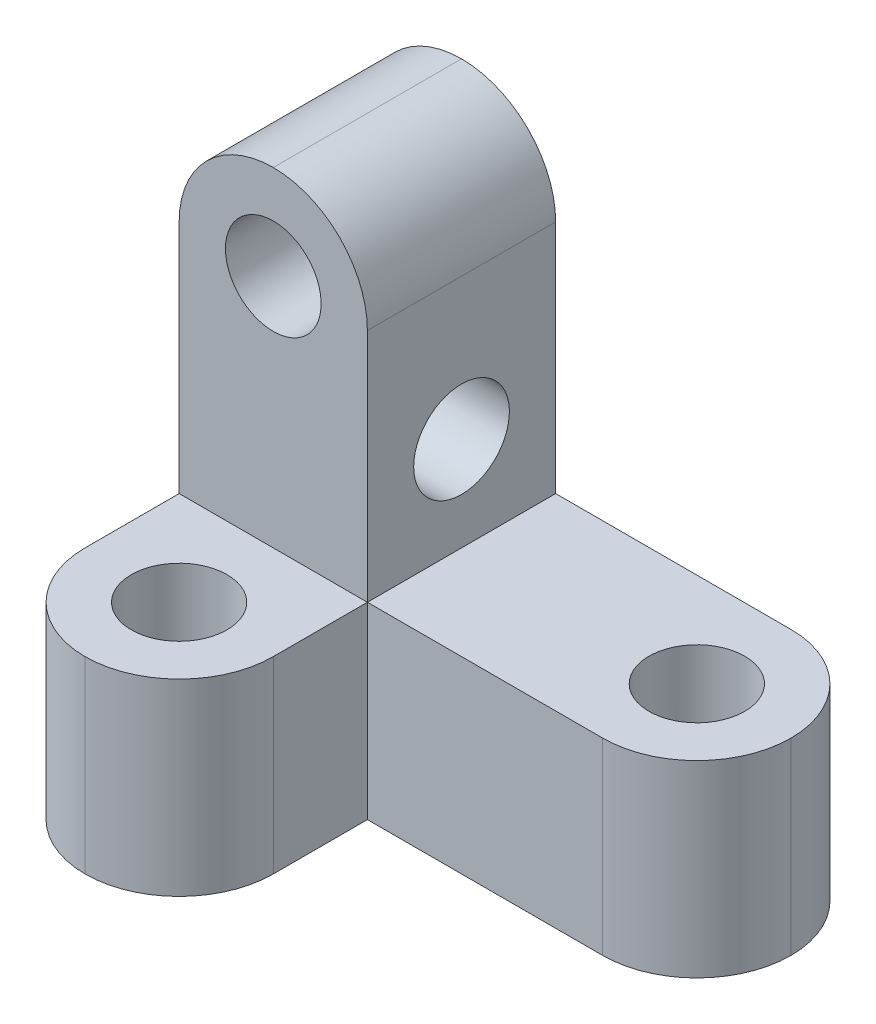
SolidWorks part; units mm, degrees
ref_plane "Front Plane" through (0, 0, 0) normal (0, 0, 1) x (1, 0, 0)
ref_plane "Top Plane" through (0, 0, 0) normal (0, 1, 0) x (1, 0, 0)
ref_plane "Right Plane" through (0, 0, 0) normal (1, 0, 0) x (0, 0, -1)
sketch "Sketch1" plane through (0, 0, 0) normal (0, 1, 0) x (1, 0, 0)
  line L1 (0, 0) -> (33, 0)
  line L2 (0, 0) -> (0, -24)
  line L3 (0, -24) -> (33, -24)
  line L4 (33, 0) -> (33, -24)
  dimension "D1" = 33
  dimension "D2" = 24
extrude "Boss-Extrude1" add sketch "Sketch1" along normal blind 33
sketch "Sketch2" plane through (0, 0, 24) normal (0, 0, 1) x (1, 0, 0)
  line L0 (0, 33) -> (0, 0) construction
  line L1 (33, 33) -> (12, 33)
  line L2 (33, 33) -> (33, 12)
  line L3 (33, 12) -> (12, 12)
  line L4 (12, 33) -> (12, 12)
  line L5 (0, 0) -> (33, 0) construction
  dimension "D1" = 12
  dimension "D2" = 12
extrude "Cut-Extrude1" cut sketch "Sketch2" against normal through all
sketch "Sketch3" plane through (0, 0, 0) normal (0, -1, 0) x (1, 0, 0)
  line L0 (33, 0) -> (0, 0) construction
  line L1 (33, 24) -> (12, 24)
  line L2 (33, 24) -> (33, 12)
  line L3 (33, 12) -> (12, 12)
  line L4 (12, 24) -> (12, 12)
  line L5 (0, 0) -> (0, 24) construction
  dimension "D1" = 12
  dimension "D2" = 12
extrude "Cut-Extrude2" cut sketch "Sketch3" against normal through all
sketch "Sketch4" plane through (0, 0, 0) normal (-1, 0, 0) x (0, 0, 1)
  line L0 (0, 33) -> (0, 0) construction
  line L1 (24, 33) -> (12, 33)
  line L2 (24, 33) -> (24, 12)
  line L3 (24, 12) -> (12, 12)
  line L4 (12, 33) -> (12, 12)
  line L5 (0, 0) -> (24, 0) construction
  dimension "D1" = 12
  dimension "D2" = 12
extrude "Cut-Extrude3" cut sketch "Sketch4" against normal through all
sketch "Sketch5" plane through (0, 0, 0) normal (-1, 0, 0) x (0, 0, 1)
  line L3 (6, 33) -> (6, 0) construction
  line L4 (0, 33) -> (12, 33) construction
  line L5 (0, 0) -> (24, 0) construction
  line L7 (12, 12) -> (24, 12) construction
  circle A1 centre (6, 18) radius 3.05
  dimension "D4" = 6.1
  dimension "D3" = 6
extrude "Cut-Extrude4" cut sketch "Sketch5" against normal through all
sketch "Sketch6" plane through (0, 0, 0) normal (0, -1, 0) x (1, 0, 0)
  line L0 (33, 6) -> (0, 6) construction
  line L1 (33, 12) -> (33, 0) construction
  line L2 (0, 0) -> (0, 24) construction
  line L3 (6, 24) -> (6, 0) construction
  line L4 (0, 24) -> (12, 24) construction
  line L5 (33, 0) -> (0, 0) construction
  line L6 (12, 12) -> (33, 12) construction
  circle A0 centre (6, 18) radius 3.05
  circle A1 centre (27, 6) radius 3.05
  dimension "D3" = 6.1
  dimension "D4" = 6.1
  dimension "D1" = 6
  dimension "D2" = 15
extrude "Cut-Extrude5" cut sketch "Sketch6" against normal through all
sketch "Sketch7" plane through (0, 0, 0) normal (0, 0, -1) x (-1, 0, 0)
  line L3 (-6, 33) -> (-6, 0) construction
  line L4 (-12, 33) -> (0, 33) construction
  line L5 (-33, 0) -> (0, 0) construction
  circle A1 centre (-6, 27) radius 3.05
  dimension "D4" = 6.1
  dimension "D2" = 15
extrude "Cut-Extrude6" cut sketch "Sketch7" against normal through all
fillet "Fillet1" radius 6 6 edges at (12, 33, 6) (0, 33, 6) (33, 6, 0) (33, 6, 12) (0, 6, 24) (12, 6, 24)
